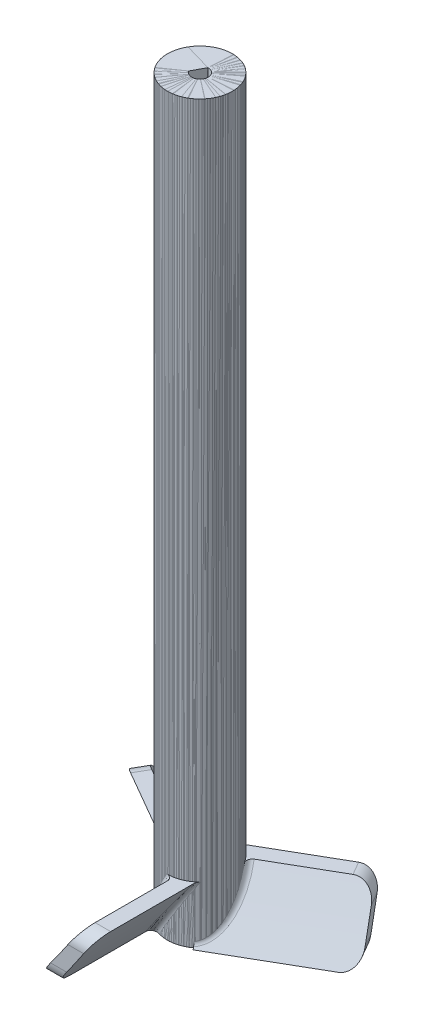
SolidWorks part; units mm, degrees
ref_plane "Front Plane" through (0, 0, 0) normal (0, 0, 1) x (1, 0, 0)
ref_plane "Top Plane" through (0, 0, 0) normal (0, 1, 0) x (1, 0, 0)
ref_plane "Right Plane" through (0, 0, 0) normal (1, 0, 0) x (0, 0, -1)
sketch "Sketch7" plane through (0, 0, 0) normal (0, 0, 1) x (1, 0, 0)
  line L0 (3.5176, 0) -> (-3.5176, 0) construction
  line L1 (6.849, 7) -> (4.9497, 7)
  line L2 (0, 0) -> (2, 0)
  arc A0 (0, 0) -> (4.9497, 7) centre (-91.3778, 69.8639) ccw
  arc A1 (6.849, 7) -> (2, 0) centre (-91.3778, 69.8639) cw
  dimension "D2" = 7
extrude "Boss-Extrude2" add sketch "Sketch7" along normal blind 15 contours A0 L1 A1 L2
fillet "Fillet1" radius 2 2 edges at (1, 0, 15) (5.8994, 7, 15)
sketch "Sketch10" plane through (0, 0, 0) normal (0, 1, 0) x (1, 0, 0)
  line L0 (0.3156, 0) -> (8.1957, 0) construction
  line L1 (4.9497, 0) -> (0, 0) construction
  line L2 (6.849, 0) -> (4.9497, 0) construction
  line L3 (2, 0) -> (6.849, 0) construction
  line L4 (4.2556, 0) -> (4.2556, 0.5251)
  line L5 (3.1481, -1000) -> (3.1481, 49000) construction
  circle A0 centre (4.2556, 0.5251) radius 3.9749
  point P5 (3.1481, 0)
  point P10 (-1.8519, 0)
  point P17 (3.1481, 0)
  dimension "D4" = 5
extrude "Boss-Extrude3" add sketch "Sketch10" along normal blind 90 contours A0 region at (0.3932, 0, -0.5251)
fillet "Fillet4" radius 0.7 2 edges at (1.2681, 1.6905, 2.0967) (3.7358, 2.3821, 3.4156)
pattern_circular "CirPattern1" count 3 over 360 about axis through (4.2556, 90, -0.5251) along (0, -1, 0) of bodies 103 102
sketch "Sketch11" plane through (0, 90, 0) normal (0, 1, 0) x (1, 0, 0)
  line L0 (3.4046, 0) -> (4.2264, 1.5247)
  arc A1 (3.4046, 0) -> (4.2264, 1.5247) centre (4.2556, 0.5251) ccw
  circle A2 centre (4.2556, 0.5251) radius 3.9749 construction
extrude "Cut-Extrude1" cut sketch "Sketch11" against normal blind 40 contours A1 L0
equation "\"insidebladediameter\"=0.01"
equation "\"height\"= 0.007"
equation "\"bladethickness\"=0.002"
equation "\"insidebladeradius\"= \"insidebladediameter\" / 2"
equation "\"D1@Sketch7\"=\"bladethickness\""
equation "\"D2@Sketch7\"=\"height\""
equation "\"bladewidth\"= \"height\" * cos ( \"bladeangle\" )"
equation "\"bladelength\"= 0.015"
equation "\"D1@Boss-Extrude2\"=\"bladelength\""
equation "\"bladetipradius\"= 0.002"
equation "\"D1@Fillet1\"=\"bladetipradius\""
equation "\"fusedistance\"= 0.0045"
equation "\"motorrodheight\"=0.09"
equation "\"D1@Boss-Extrude3\"=\"motorrodheight\""
equation "\"numberofblades\"= 3"
equation "\"D1@CirPattern1\"=\"numberofblades\""
equation "\"roddiameter\"= ( \"bladewidth\" + 0.003 )"
equation "\"roddepth\"= 0.005"
equation "\"bladeangle\"= 45deg"
equation "\"m\"=1"
equation "\"flatfacedist\"= 0.0005"
equation "\"motorshaftdiameter\"=0.002"
equation "\"D1@Sketch11\"=\"motorshaftdiameter\"/2"
equation "\"D3@Sketch7\"=\"bladewidth\""
equation "\"D2@Sketch10\"=\"roddiameter\"/2-\"fusedistance\""
equation "\"D1@Sketch10\"=\"roddiameter\""
equation "\"D2@Sketch11\"=\"flatfacedist\""
equation "\"bladefilletradius\"= 0.0007"
equation "\"D1@Fillet4\"=\"bladefilletradius\""
